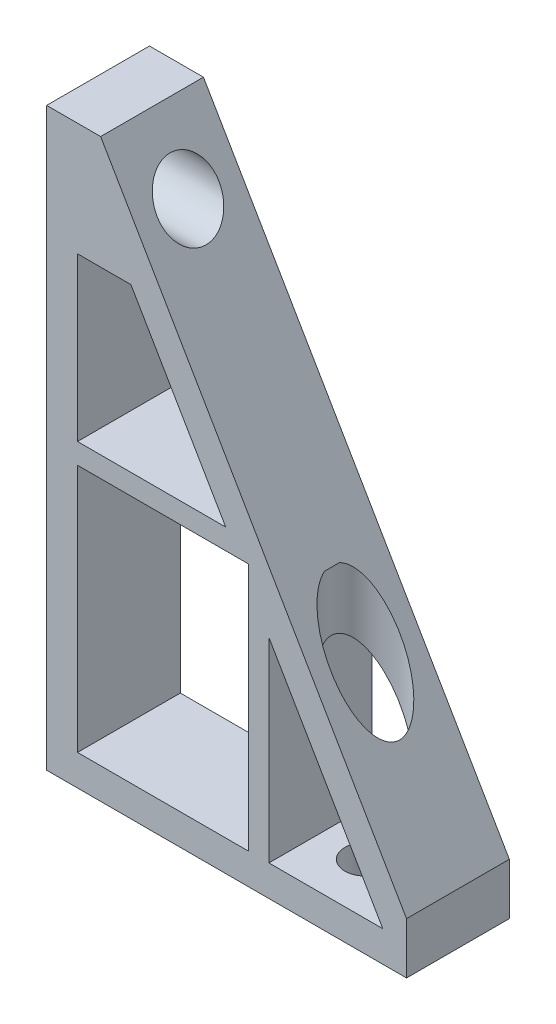
SolidWorks part; units mm, degrees
material "Magnesium Alloy"
ref_plane "Front Plane" through (0, 0, 0) normal (0, 0, 1) x (1, 0, 0)
ref_plane "Top Plane" through (0, 0, 0) normal (0, 1, 0) x (1, 0, 0)
ref_plane "Right Plane" through (0, 0, 0) normal (1, 0, 0) x (0, 0, -1)
sketch "Sketch1" plane through (0, 0, 0) normal (0, 0, 1) x (1, 0, 0)
  line L0 (0, 0) -> (44.45, 0)
  line L1 (55, 0) -> (-55, 0) construction
  line L2 (44.45, 0) -> (44.45, 6.35)
  line L3 (44.45, 6.35) -> (0, 82.55)
  line L4 (0, -55) -> (0, 55) construction
  line L5 (0, 82.55) -> (0, 0)
  dimension "D1" = 82.55
  dimension "D2" = 6.35
  dimension "D3" = 44.45
extrude "Boss-Extrude1" add sketch "Sketch1" along normal blind 12.7
sketch "Sketch3" plane through (0, 0, 0) normal (0, 0, 1) x (1, 0, 0)
  line L0 (3.81, 37.0675) -> (22.1206, 37.0675)
  line L1 (22.1206, 37.0675) -> (10.4058, 57.15)
  line L2 (3.81, 57.15) -> (3.81, 37.0675)
  line L3 (3.81, 34.5275) -> (24.915, 34.5275)
  line L4 (24.915, 34.5275) -> (24.915, 3.81)
  line L5 (24.915, 3.81) -> (3.81, 3.81)
  line L6 (3.81, 3.81) -> (3.81, 34.5275)
  line L7 (27.455, 3.81) -> (41.5208, 3.81)
  line L8 (41.5208, 3.81) -> (27.455, 27.9228)
  line L9 (27.455, 27.9228) -> (27.455, 3.81)
  line L10 (44.45, 6.35) -> (0, 82.55) construction
  line L11 (6.985, 0) -> (-6.985, 0) construction
  line L12 (0, -6.985) -> (0, 6.985) construction
  line L13 (6.6675, 71.12) -> (0, 71.12)
  line L14 (0, 71.12) -> (0, 82.55)
  line L15 (0, 82.55) -> (6.6675, 71.12)
  line L16 (10.4058, 57.15) -> (3.81, 57.15)
  dimension "D1" = 3.81
  dimension "D2" = 3.81
  dimension "D3" = 3.81
  dimension "D4" = 2.54
  dimension "D5" = 2.54
  dimension "D6" = 3.81
  dimension "D7" = 3.81
  dimension "D8" = 11.43
  dimension "D9" = 25.4
extrude "Cut-Extrude1" cut sketch "Sketch3" against normal blind 25.4 and the other way blind 26.162
sketch "Sketch4" plane through (0, 0, 0) normal (0, -1, 0) x (1, 0, 0)
  line L0 (44.45, 12.7) -> (44.45, 0) construction
  line L1 (0, 12.7) -> (44.45, 12.7) construction
  circle A0 centre (33.02, 6.35) radius 2.54
  dimension "D3" = 5.08
  dimension "D1" = 11.43
  dimension "D2" = 6.35
extrude "Cut-Extrude2" cut sketch "Sketch4" against normal blind 50.8
sketch "Sketch9" plane through (0, 3.81, 0) normal (0, 1, 0) x (1, 0, 0)
  circle A0 centre (33.02, -6.35) radius 4.2291
  dimension "D1" = 8.4582
extrude "Cut-Extrude3" cut sketch "Sketch9" along normal blind 29.21
ref_axis "Axis1" through (33.02, 3.81, 6.35) along (0, -1, 0)
ref_axis "Axis2" through (33.02, 3.81, 6.35) along (0, -1, 0)
sketch "Sketch11" plane through (3.81, 0, 0) normal (1, 0, 0) x (0, 0, -1)
  line L0 (-12.7, 71.12) -> (0, 71.12) construction
  line L1 (-12.7, 71.12) -> (-12.7, 0) construction
  circle A0 centre (-6.35, 63.5) radius 3.81
  dimension "D1" = 7.62
  dimension "D2" = 7.62
  dimension "D3" = 6.35
extrude "Cut-Extrude4" cut sketch "Sketch11" along normal blind 12.7
sketch "Sketch12" plane through (3.81, 0, 0) normal (1, 0, 0) x (0, 0, -1)
  circle A0 centre (-6.35, 63.5) radius 2.54
extrude "Cut-Extrude5" cut sketch "Sketch12" against normal blind 12.7
